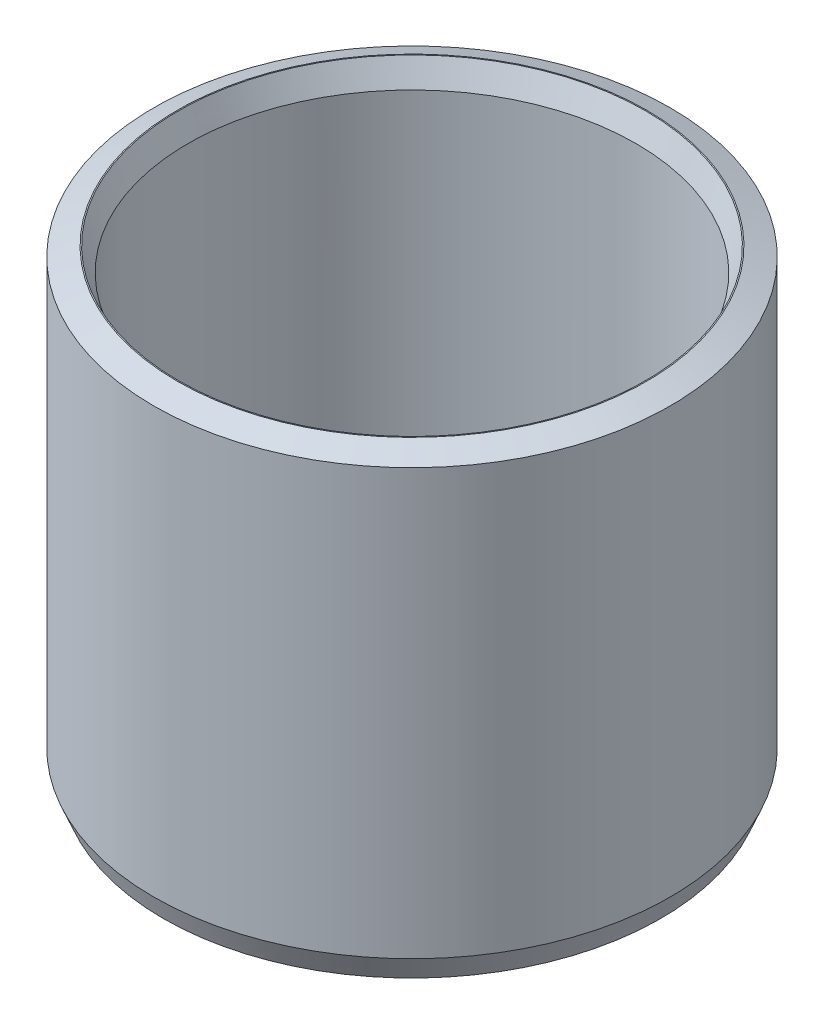
SolidWorks part; units mm, degrees
ref_plane "Front Plane" through (0, 0, 0) normal (0, 0, 1) x (1, 0, 0)
ref_plane "Top Plane" through (0, 0, 0) normal (0, 1, 0) x (1, 0, 0)
ref_plane "Right Plane" through (0, 0, 0) normal (1, 0, 0) x (0, 0, -1)
sketch "Sketch1" plane through (0, 0, 0) normal (0, 1, 0) x (1, 0, 0)
  circle A0 centre (0, 0) radius 42.5
  dimension "SLEEVE_OD" = 85
extrude "Boss-Extrude1" add sketch "Sketch1" along normal blind 75.4359
sketch "Sketch2" plane through (0, 0, 0) normal (0, 1, 0) x (1, 0, 0)
  circle A0 centre (0, 0) radius 36.8655
  dimension "BORE_D" = 73.731
extrude "Cut-Extrude1" cut sketch "Sketch2" along normal through all
chamfer "Chamfer1" distance 1.5831 angle 67.75 4 edges at (0, 75.4359, 36.8655) (0, 0, 36.8655) (0, 0, 42.5) (0, 75.4359, 42.5) first distance on face at (0, 75.4359, 36.8655) first distance on face at (0, 0, 36.8655) first distance on face at (0, 75.4359, 42.5)
